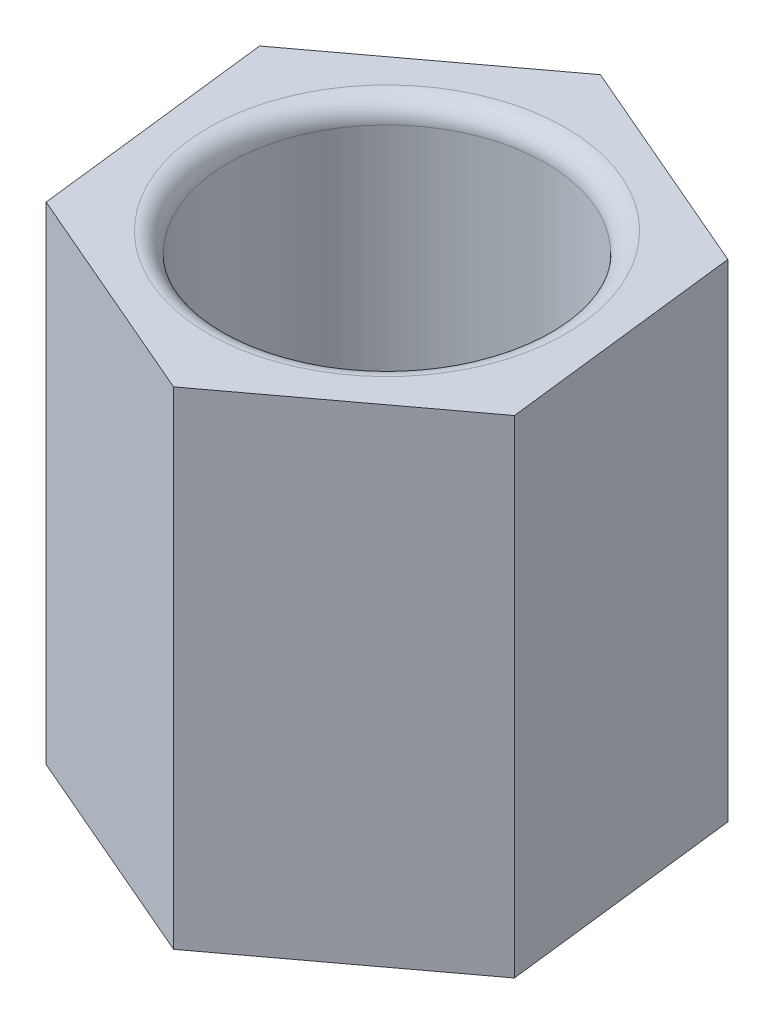
SolidWorks part; units mm, degrees
ref_plane "Front Plane" through (0, 0, 0) normal (0, 0, 1) x (1, 0, 0)
ref_plane "Top Plane" through (0, 0, 0) normal (0, 1, 0) x (1, 0, 0)
ref_plane "Right Plane" through (0, 0, 0) normal (1, 0, 0) x (0, 0, -1)
sketch "Sketch1" plane through (0, 0, 0) normal (0, 1, 0) x (1, 0, 0)
  line L1 (2.7556, -1.1861) -> (2.405, 1.7933)
  line L2 (2.405, 1.7933) -> (-0.3506, 2.9794)
  line L3 (-0.3506, 2.9794) -> (-2.7556, 1.1861)
  line L4 (-2.7556, 1.1861) -> (-2.405, -1.7933)
  line L5 (-2.405, -1.7933) -> (0.3506, -2.9794)
  line L6 (0.3506, -2.9794) -> (2.7556, -1.1861)
  circle A0 centre (0, 0) radius 2.5981 construction
  dimension "D1" = 6
extrude "Boss-Extrude1" add sketch "Sketch1" along normal blind 6
sketch "Sketch2" plane through (0, 6, 0) normal (0, 1, 0) x (1, 0, 0)
  circle A0 centre (0, 0) radius 1.95
  dimension "D1" = 3.9
extrude "Cut-Extrude1" cut sketch "Sketch2" against normal blind 5
fillet "Fillet1" radius 0.25 1 edges at (0, 6, 1.95)
